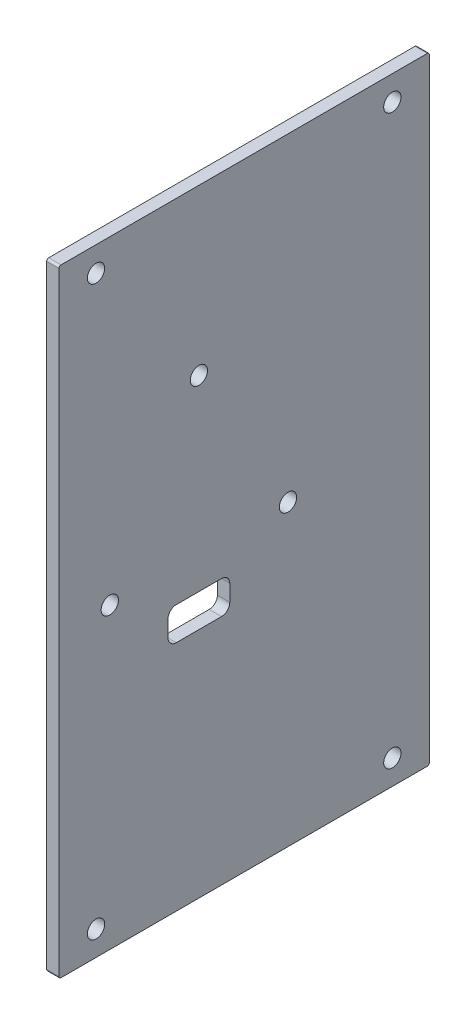
SolidWorks part; units mm, degrees
material "ABS"
ref_plane "Front Plane" through (0, 0, 0) normal (0, 0, 1) x (1, 0, 0)
ref_plane "Top Plane" through (0, 0, 0) normal (0, 1, 0) x (1, 0, 0)
ref_plane "Right Plane" through (0, 0, 0) normal (1, 0, 0) x (0, 0, -1)
sketch "Sketch1" plane through (0, 0, 0) normal (1, 0, 0) x (0, 0, -1)
  line L0 (34, -85.5) -> (28.5, -85.5)
  line L1 (0, 0) -> (90, 0)
  line L2 (0, 0) -> (0, -150)
  line L3 (0, -150) -> (90, -150)
  line L4 (90, 0) -> (90, -150)
  line L5 (26.5, -87.5) -> (26.5, -91.5)
  line L6 (34, -65) -> (34, -85.5) construction
  line L7 (28.5, -93.5) -> (39.5, -93.5)
  line L8 (41.5, -91.5) -> (41.5, -87.5)
  line L9 (39.5, -85.5) -> (34, -85.5)
  line L10 (45, 0) -> (45, -150) construction
  line L11 (0, -75) -> (90, -75) construction
  circle A0 centre (34, -65) radius 5 construction
  circle A1 centre (34, -40) radius 2.1
  circle A2 centre (55.6506, -77.5) radius 2.1
  circle A3 centre (12.3494, -77.5) radius 2.1
  arc A4 (41.5, -91.5) -> (39.5, -93.5) centre (39.5, -91.5) cw
  arc A5 (39.5, -85.5) -> (41.5, -87.5) centre (39.5, -87.5) cw
  arc A6 (28.5, -93.5) -> (26.5, -91.5) centre (28.5, -91.5) cw
  arc A7 (26.5, -87.5) -> (28.5, -85.5) centre (28.5, -87.5) cw
  circle A8 centre (9, -6) radius 2.1
  circle A9 centre (81, -6) radius 2.1
  circle A10 centre (81, -144) radius 2.1
  circle A11 centre (9, -144) radius 2.1
  point P21 (41.5, -93.5)
  point P26 (26.5, -93.5)
  point P29 (26.5, -85.5)
  dimension "D5" = 10
  dimension "D7" = 4.2
  dimension "D13" = 2
  dimension "D17" = 4.2
  dimension "D3" = 65
  dimension "D4" = 34
  dimension "D6" = 25
  dimension "D9" = 20.5
  dimension "D10" = 7.5
  dimension "D11" = 15
  dimension "D12" = 8
  dimension "D14" = 90
  dimension "D2" = 150
  dimension "D15" = 9
  dimension "D16" = 6
  dimension "D8" = 3
extrude "Boss-Extrude1" add sketch "Sketch1" along normal blind 3
fillet "Fillet1" radius 0.5 4 edges at (1.5, -150, -90) (1.5, -150, 0) (1.5, 0, -90) (1.5, 0, 0)
equation "\"Depth\"= 90mm"
equation "\"Height\" = 150mm"
equation "\"Width\"= 64mm"
equation "\"D14@Sketch1\"=\"Depth\""
equation "\"D2@Sketch1\"=\"Height\""
